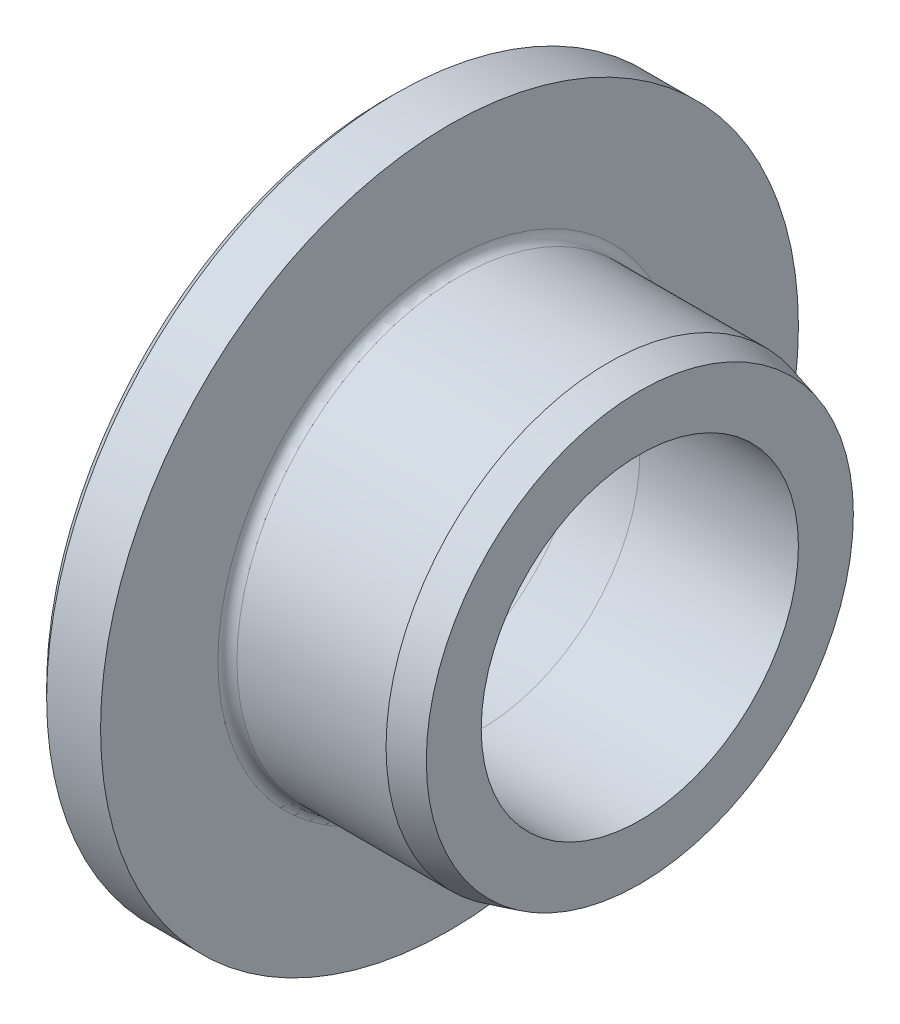
SolidWorks part; units mm, degrees
material "黄銅"
ref_plane "Front Plane" through (0, 0, 0) normal (0, 0, 1) x (1, 0, 0)
ref_plane "Top Plane" through (0, 0, 0) normal (0, 1, 0) x (1, 0, 0)
ref_plane "Right Plane" through (0, 0, 0) normal (1, 0, 0) x (0, 0, -1)
ref_axis "Axis_X" through (0, 0, 0) along (1, 0, 0)
ref_axis "Axis_Y" through (0, 0, 0) along (0, 1, 0)
ref_axis "Axis_Z" through (0, 0, 0) along (0, 0, 1)
sketch "Sketch1" plane through (0, 0, 0) normal (0, 0, 1) x (1, 0, 0)
  line L0 (-2, 0) -> (8, 0) construction
  line L1 (-2, 5) -> (6, 5)
  line L2 (6, 5) -> (6, 7)
  line L3 (6, 7) -> (0, 7)
  line L4 (0, 7) -> (0, 11)
  line L5 (0, 11) -> (-2, 11)
  line L6 (-2, 11) -> (-2, 5)
  dimension "D_s" = 10
  dimension "H" = 22
  dimension "L" = 8
  dimension "D" = 14
  dimension "T_s" = 2
revolve "Revolve1" add sketch "Sketch1" angle 360 about L0
chamfer "Chamfer1" distance 0.3 angle 45 1 edges at (-2, 0, 11)
fillet "Fillet1" radius 0.3 1 edges at (0, 0, 7)
chamfer "Chamfer2" distance 3 angle 10 1 edges at (-2, 0, 5) first distance on face at (6, 0, 5)
chamfer "Chamfer3" distance 1 angle 15 1 edges at (6, 0, 7) first distance on face at (0.3, 0, 7)
chamfer "Chamfer4" [suppressed] distance 1 angle 10
fillet "Fillet2" radius 1 1 edges at (-2, 0, -5.529)
